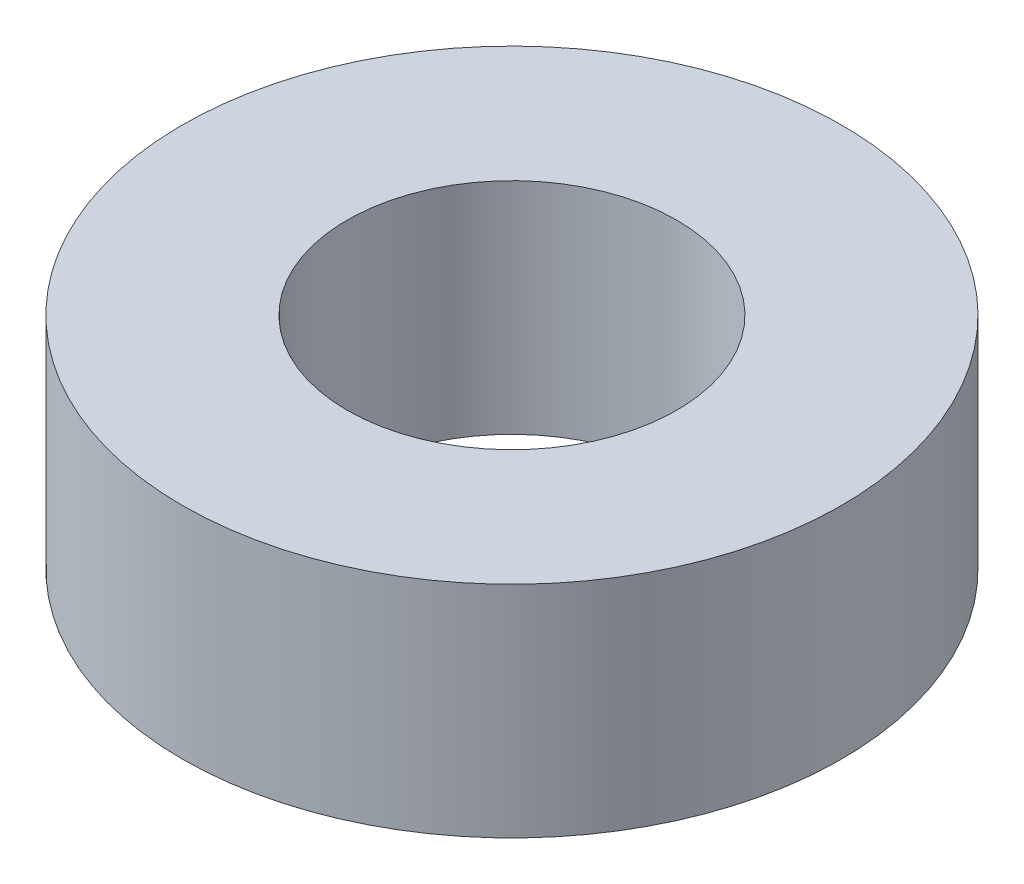
SolidWorks part; units mm, degrees
ref_plane "Front Plane" through (0, 0, 0) normal (0, 0, 1) x (1, 0, 0)
ref_plane "Top Plane" through (0, 0, 0) normal (0, 1, 0) x (1, 0, 0)
ref_plane "Right Plane" through (0, 0, 0) normal (1, 0, 0) x (0, 0, -1)
sketch "Sketch1" plane through (0, 0, 0) normal (0, 1, 0) x (1, 0, 0)
  circle A0 centre (0, 0) radius 45
  dimension "FLANGE_OD" = 90
extrude "Boss-Extrude1" add sketch "Sketch1" along normal blind 30
sketch "Sketch2" plane through (0, 0, 0) normal (0, 1, 0) x (1, 0, 0)
  circle A0 centre (0, 0) radius 22.5
  dimension "BORE_D" = 45
extrude "Cut-Extrude1" cut sketch "Sketch2" along normal through all
sketch "Sketch3" plane through (0, 30, 0) normal (0, 1, 0) x (1, 0, 0)
  circle A0 centre (0, 0) radius 14.2128 construction
  circle A1 centre (-14.2128, 0) radius 1.6893
  dimension "BOLT_D" = 3.3786
  dimension "BOLT_PCD" = 28.4257
extrude "Cut-Extrude2" cut sketch "Sketch3" against normal blind 24.9178 rebuild error yes
pattern_circular "CirPattern1" count 4 over 360 rebuild error yes
